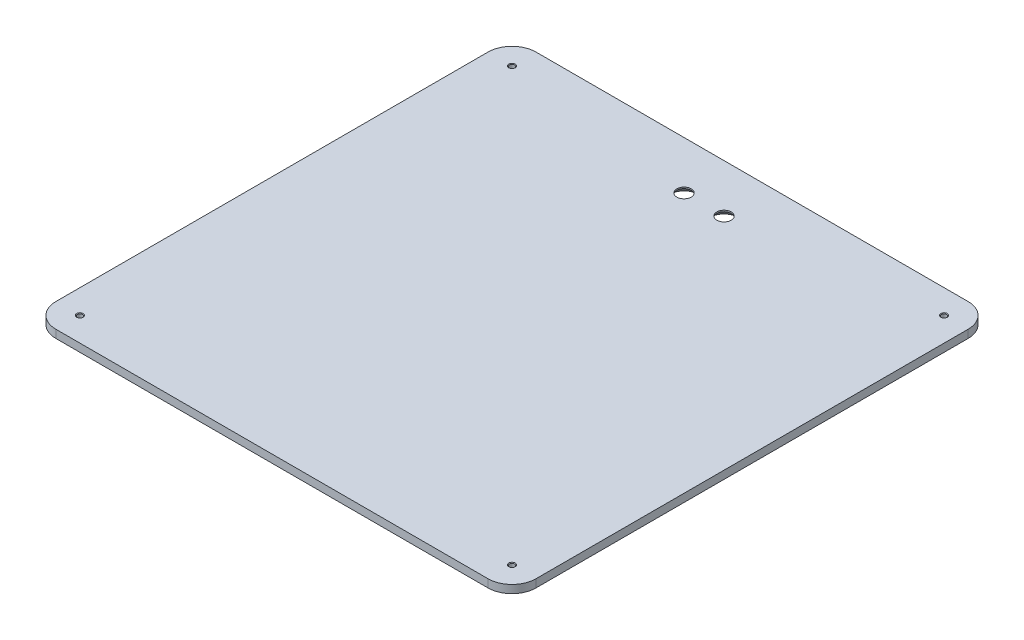
SolidWorks part; units mm, degrees
note: The reader was unsure of these and kept them because the rebuilt part matched: thickness of "Tôle de base pliée1", "Tôlerie1", "Tôlerie10", "Tôlerie11".
ref_plane "Plan de face" through (0, 0, 0) normal (0, 0, 1) x (1, 0, 0)
ref_plane "Plan de dessus" through (0, 0, 0) normal (0, 1, 0) x (1, 0, 0)
ref_plane "Plan de droite" through (0, 0, 0) normal (1, 0, 0) x (0, 0, -1)
sketch "Esquisse1" plane through (0, 0, 0) normal (0, 1, 0) x (1, 0, 0)
  line L1 (150, 150) -> (-150, 150)
  line L2 (150, 150) -> (150, -150)
  line L3 (150, -150) -> (-150, -150)
  line L4 (-150, 150) -> (-150, -150)
  line L5 (150, 150) -> (-150, -150) construction
  line L6 (150, -150) -> (-150, 150) construction
  point P0 (0, 0)
  dimension "D1" = 300
base flange "Tôle de base pliée1" sketch "Esquisse1" thickness 5 reverse thickness direction no parameters "D1"=0.7366
hole_wizard "Fraisage pour vis à tête fraisée M81" positions "Esquisse2" profile "Esquisse3" countersink size "M8" standard "DIN" end condition up to next
sketch "Esquisse2" plane through (0, -5, 0) normal (0, -1, 0) x (-1, 0, 0)
  line L12 (0, 150) -> (0, 120) construction
  line L13 (-150, 150) -> (150, 150) construction
  line L15 (-12.5, 120) -> (12.5, 120) construction
  point P0 (-12.5, 120)
  point P45 (12.5, 120)
  dimension "D1" = 30
  dimension "D2" = 25
sketch "Esquisse3" plane through (12.5, -5, -120) normal (1, 0, 0) x (0, 0, -1)
  line L0 (0, 0) -> (0, 5)
  line L1 (0, 5) -> (4.5, 5)
  line L2 (4.5, 5) -> (4.5, 4.15)
  line L3 (4.5, 4.15) -> (8.65, 0)
  line L5 (8.65, 0) -> (0, 0)
  line L6 (-4.5, 4.15) -> (-8.65, 0) construction
  line L11 (0, -6.35) -> (0, 107.95) construction
  dimension "Diamètre du perçage jusqu'au prochain" = 9
  dimension "Profondeur du perçage jusqu'au prochain" = 5
  dimension "Diamètre du fraisage entrant" = 17.3
  dimension "Angle du fraisage entrant" = 90
hole_wizard "Trou taraudé M41" positions "Esquisse4" profile "Esquisse5" tap size "M4" standard "DIN" end condition up to next
sketch "Esquisse4" plane through (0, 0, 0) normal (0, 1, 0) x (1, 0, 0)
  line L1 (-150, -150) -> (150, 150) construction
  line L4 (150, -150) -> (-150, 150) construction
  line L6 (150, 150) -> (-150, 150) construction
  point P0 (135, -135)
  point P2 (-135, -135)
  point P4 (-135, 135)
  point P6 (135, 135)
  dimension "D1" = 15
sketch "Esquisse5" plane through (135, 0, 135) normal (1, 0, 0) x (0, 0, 1)
  line L0 (0, 0) -> (0, 5)
  line L1 (0, 5) -> (1.65, 5)
  line L2 (1.65, 5) -> (1.65, 0.375)
  line L3 (1.65, 0.375) -> (2.025, 0)
  line L5 (2.025, 0) -> (0, 0)
  line L6 (-1.65, 0.375) -> (-2.025, 0) construction
  line L11 (0, -6.35) -> (0, 107.95) construction
  dimension "Diamètre du trou pour taraudage jusqu'au prochain" = 3.3
  dimension "Profondeur du trou pour taraudage jusqu'au prochain" = 5
  dimension "Diamètre du fraisage entrant" = 4.05
  dimension "Angle du fraisage entrant" = 90
cosmetic thread "Filetage de perçage1"
cosmetic thread "Filetage de perçage2"
cosmetic thread "Filetage de perçage3"
cosmetic thread "Filetage de perçage4"
fillet "Congé1" radius 15 4 edges at (150, -2.5, -150) (150, -2.5, 150) (-150, -2.5, 150) (-150, -2.5, -150)
sketch "Lignes de pliage1" [suppressed] plane through (0, 0, 0) normal (0, 1, 0) x (1, 0, 0)
sketch "Cube de visualisation1" [suppressed] plane through (0, 0, 0) normal (0, 1, 0) x (1, 0, 0)
sheet metal parameters "Tôlerie1" thickness 5 parameters "D1"=0.7366
flat pattern "Etat déplié1" [suppressed]
sketch "Lignes de pliage2" plane through (0, 0, 0) normal (0, 1, 0) x (1, 0, 0)
sketch3d "Cube de visualisation2" [suppressed]
  line L0 (246.3397, -107.5833, 0) -> (83.6603, -389.3524, 0) construction
  line L1 (-2.3205, 35.9807, 0) -> (-165, -245.7884, 0) construction
  line L2 (246.3397, -107.5833, 0) -> (-2.3205, 35.9807, 0) construction
  line L3 (83.6603, -389.3524, 0) -> (-165, -245.7884, 0) construction
sheet metal parameters "Tôlerie10" thickness 5 parameters "D1"=0.7366
flat pattern "Etat déplié1"
sketch "Lignes de pliage2" plane through (0, 0, 0) normal (0, 1, 0) x (1, 0, 0)
sketch3d "Cube de visualisation2" [suppressed]
  line L0 (-150, 150, 0) -> (150, 150, 0) construction
  line L1 (-150, -150, 0) -> (150, -150, 0) construction
  line L2 (-150, 150, 0) -> (-150, -150, 0) construction
  line L3 (150, 150, 0) -> (150, -150, 0) construction
sheet metal parameters "Tôlerie11" thickness 5 parameters "D1"=0.7366
flat pattern "Etat déplié1"
sketch "Lignes de pliage2" plane through (0, 0, 0) normal (0, 1, 0) x (1, 0, 0)
sketch3d "Cube de visualisation2" [suppressed]
  line L0 (-150, 150, 0) -> (150, 150, 0) construction
  line L1 (-150, -150, 0) -> (150, -150, 0) construction
  line L2 (-150, 150, 0) -> (-150, -150, 0) construction
  line L3 (150, 150, 0) -> (150, -150, 0) construction
equation "\"e\"= 15mm"
